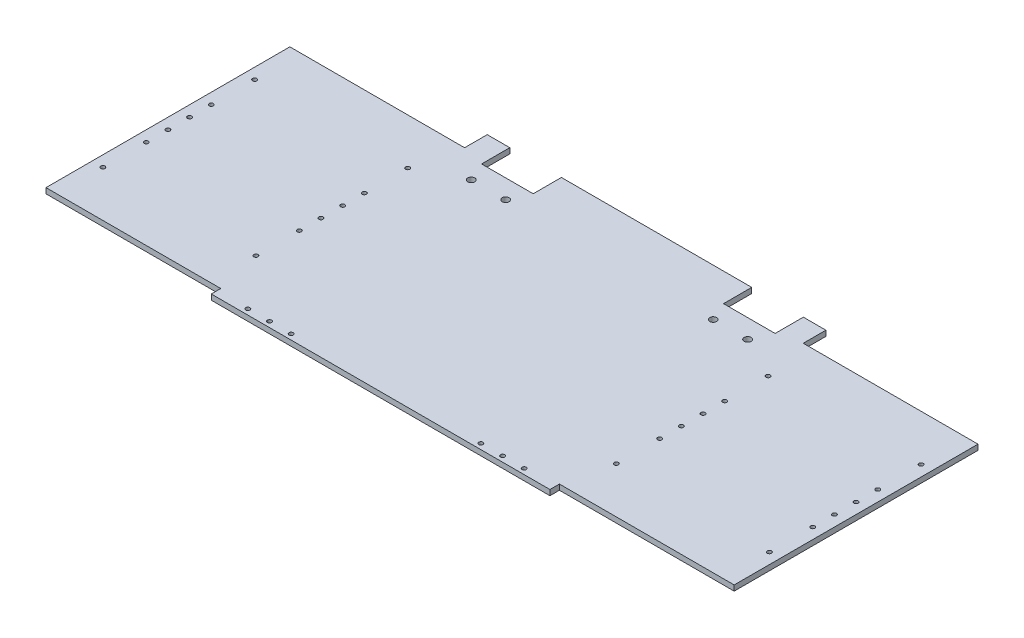
SolidWorks part; units mm, degrees
ref_plane "Front Plane" through (0, 0, 0) normal (0, 0, 1) x (1, 0, 0)
ref_plane "Top Plane" through (0, 0, 0) normal (0, 1, 0) x (1, 0, 0)
ref_plane "Right Plane" through (0, 0, 0) normal (1, 0, 0) x (0, 0, -1)
sketch "Sketch1" plane through (0, 0, 0) normal (0, 1, 0) x (1, 0, 0)
  line L0 (129, 0) -> (129, -7)
  line L1 (0, 0) -> (129, 0)
  line L2 (0, 0) -> (0, 180)
  line L3 (0, 180) -> (129, 180)
  line L4 (508, 0) -> (508, 180)
  line L5 (129, -7) -> (379, -7)
  line L6 (379, -7) -> (379, 0)
  line L7 (0, 90) -> (508, 90) construction
  line L8 (129, 180) -> (129, 196.718)
  line L9 (129, 196.718) -> (145.65, 196.718)
  line L10 (379, 196.718) -> (379, 180)
  line L11 (254, 195.398) -> (254, -38.1) construction
  line L12 (379, 0) -> (508, 0)
  line L13 (379, 180) -> (508, 180)
  line L14 (129, 161.92) -> (379, 161.92) construction
  line L15 (129, -3) -> (254, -3) construction
  line L16 (145.65, 196.718) -> (145.65, 175.89)
  line L17 (145.65, 175.89) -> (183.75, 175.89)
  line L18 (183.75, 175.89) -> (183.75, 196.718)
  line L19 (183.75, 196.718) -> (324.25, 196.718)
  line L20 (324.25, 175.89) -> (362.35, 175.89)
  line L21 (362.35, 196.718) -> (379, 196.718)
  line L23 (362.35, 196.718) -> (362.35, 175.89)
  line L24 (324.25, 175.89) -> (324.25, 196.718)
  circle A0 centre (152, 161.92) radius 2.564
  circle A1 centre (177.4, 161.92) radius 2.564
  circle A4 centre (152, -3) radius 1.55
  circle A5 centre (184, -3) radius 1.55
  circle A8 centre (330.6, 161.92) radius 2.564
  circle A9 centre (356, 161.92) radius 2.564
  circle A10 centre (168, -3) radius 1.55
  circle A11 centre (324, -3) radius 1.55
  circle A12 centre (340, -3) radius 1.55
  circle A13 centre (356, -3) radius 1.55
  circle A14 centre (121, 146) radius 1.55
  circle A15 centre (121, 114) radius 1.55
  circle A16 centre (121, 98) radius 1.55
  circle A17 centre (121, 82) radius 1.55
  circle A18 centre (121, 66) radius 1.55
  circle A19 centre (121, 34) radius 1.55
  circle A20 centre (387, 146) radius 1.55
  circle A21 centre (387, 114) radius 1.55
  circle A22 centre (387, 98) radius 1.55
  circle A23 centre (387, 82) radius 1.55
  circle A24 centre (387, 66) radius 1.55
  circle A25 centre (387, 34) radius 1.55
  circle A26 centre (8, 146) radius 1.55
  circle A27 centre (8, 114) radius 1.55
  circle A28 centre (8, 98) radius 1.55
  circle A29 centre (8, 82) radius 1.55
  circle A30 centre (8, 66) radius 1.55
  circle A31 centre (8, 34) radius 1.55
  circle A32 centre (500, 34) radius 1.55
  circle A33 centre (500, 66) radius 1.55
  circle A34 centre (500, 82) radius 1.55
  circle A35 centre (500, 98) radius 1.55
  circle A36 centre (500, 114) radius 1.55
  circle A37 centre (500, 146) radius 1.55
  point P10 (254, 90)
  dimension "D7" = 3.1
  dimension "D9" = 5.128
  dimension "D16" = 3.1
  dimension "D21" = 3.1
  dimension "D1" = 180
  dimension "D2" = 508
  dimension "D3" = 250
  dimension "D5" = 250
  dimension "D10" = 25.4
  dimension "D11" = 23
  dimension "D12" = 16
  dimension "D13" = 16
  dimension "D14" = 23
  dimension "D15" = 4
  dimension "D4" = 3
  dimension "D17" = 32
  dimension "D19" = 16
  dimension "D20" = 8
  dimension "D18" = 8
  dimension "D22" = 8
  dimension "D23" = 16
  dimension "D24" = 32
  dimension "D25" = 8
  dimension "D8" = 16.718
  dimension "D6" = 18.08
  dimension "D26" = 6.35
  dimension "D27" = 6.35
  dimension "D28" = 13.97
  dimension "D29" = 129
extrude "Boss-Extrude1" add sketch "Sketch1" along normal blind 4
equation "\"cf_tube_outer_diameter\"= 25mm"
equation "\"cf_tube_inner_diameter\" = 21mm"
equation "\"mid_plate_mid_to_top\" = 100mm"
equation "\"mid_plate_mid_to_bottom\" = 30mm"
equation "\"mid_plate_horizontal_spacing\"=250mm"
equation "\"cf_plate_thickness\" =4mm"
equation "\"mid_tube_length\" = 121mm"
equation "\"mid_plate_bottom_width\" = 180mm"
equation "\"D1@Sketch1\"=\"mid_plate_bottom_width\""
equation "\"D1@Boss-Extrude1\"=\"cf_plate_thickness\""
equation "\"D5@Sketch1\"=\"mid_plate_horizontal_spacing\""
equation "\"D3@Sketch1\"=\"mid_plate_horizontal_spacing\""
